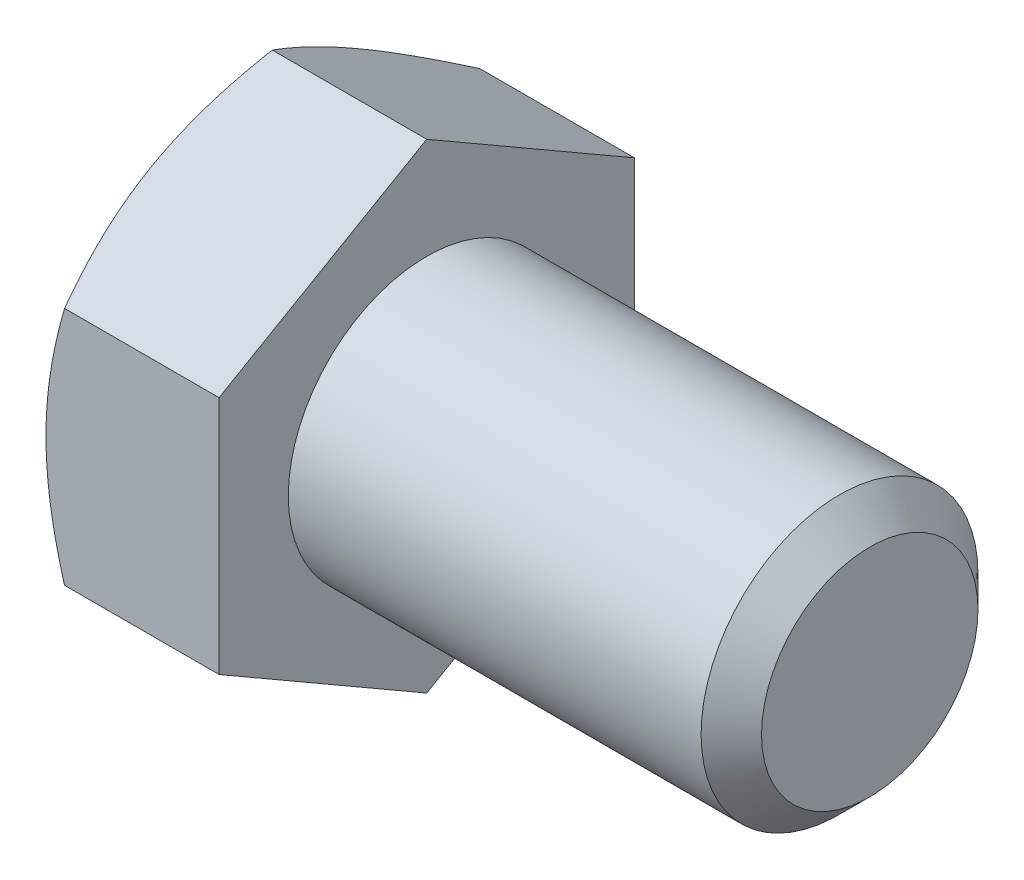
SolidWorks part; units mm, degrees
ref_plane "Front Plane" through (0, 0, 0) normal (0, 0, 1) x (1, 0, 0)
ref_plane "Top Plane" through (0, 0, 0) normal (0, 1, 0) x (1, 0, 0)
ref_plane "Right Plane" through (0, 0, 0) normal (1, 0, 0) x (0, 0, -1)
sketch "Sketch1" plane through (0, 0, 0) normal (0, 0, 1) x (1, 0, 0)
  line L0 (-17.6609, 0) -> (17.6609, 0) construction
  line L1 (17.6609, 7.9375) -> (17.6609, -7.9375) construction
  line L2 (-7.7391, 11.9062) -> (-7.7391, -11.9062) construction
  line L3 (-17.6609, 11.9062) -> (-17.6609, -11.9062) construction
  point P9 (-7.7391, 0)
  point P10 (9.5791, -7.9375)
  dimension "Screw Dia" = 15.875
  dimension "Hex" = 23.8125
  dimension "Head Ht" = 9.9219
  dimension "Screw Lenght" = 25.4
  dimension "D1" = 8.0818
ref_plane "Plane2" through (17.6609, 0, 0) normal (1, 0, 0) x (0, 0, -1)
sketch "Sketch5" plane through (17.6609, 0, 0) normal (1, 0, 0) x (0, 0, -1)
  circle A0 centre (0, 0) radius 7.9375
extrude "Boss-Extrude3" add sketch "Sketch5" against normal up to vertex (25.4 mm away) up to point (-7.7391, 0, 0)
sketch "Sketch9" plane through (17.6609, 0, 0) normal (1, 0, 0) x (0, 0, -1)
  circle A1 centre (0, 0) radius 7.9375
  circle A2 centre (0, 0) radius 7.9375
  dimension "D1" = 0
curve "Helix/Spiral1" pitch 2.3091 height 27.7091 turns 12 parameters "Pitch"=2.3091
chamfer "Chamfer1" distance 1.7318 angle 45 1 edges at (17.6609, 0, -7.9375)
sketch "Sketch10" plane through (0, 0, 0) normal (0, 0, 1) x (1, 0, 0)
  line L0 (17.6609, 7.9375) -> (18.5268, 6.4377)
  line L1 (18.5268, 6.4377) -> (18.8155, 6.4377)
  line L2 (18.8155, 6.4377) -> (19.6814, 7.9375)
  line L3 (17.6609, 7.9375) -> (19.6814, 7.9375)
  line L4 (18.6712, 7.9375) -> (18.6712, 6.4377) construction
  line L5 (18.0939, 7.1876) -> (19.2484, 7.1876) construction
  dimension "D1" = 60
  dimension "D2" = 0.2886
  dimension "D3" = 1.1545
sweep "Cut-Sweep1" [suppressed] cut profiles "Sketch10" path "Helix/Spiral1"
sketch "Sketch6" plane through (-7.7391, 0, 0) normal (-1, 0, 0) x (0, 0, 1)
  line L0 (0, 11.9062) -> (0, -11.9062) construction
  line L1 (11.9062, 6.8741) -> (0, 13.7482)
  line L2 (0, 13.7482) -> (-11.9063, 6.8741)
  line L3 (-11.9063, 6.8741) -> (-11.9063, -6.8741)
  line L4 (-11.9063, -6.8741) -> (0, -13.7482)
  line L5 (0, -13.7482) -> (11.9062, -6.8741)
  line L6 (11.9062, -6.8741) -> (11.9062, 6.8741)
  circle A0 centre (0, 0) radius 11.9062 construction
extrude "Boss-Extrude4" add sketch "Sketch6" along normal up to vertex (9.9219 mm away) up to point (-17.6609, -11.9062, 0)
sketch "Sketch7" plane through (-17.6609, 0, 0) normal (-1, 0, 0) x (0, 0, 1)
  circle A0 centre (0, 0) radius 11.9062 construction
  circle A1 centre (0, 0) radius 11.9062
sketch "Sketch8" plane through (-17.6609, 0, 0) normal (-1, 0, 0) x (0, 0, 1)
  circle A0 centre (0, 0) radius 11.9062 construction
  circle A1 centre (0, 0) radius 11.9062
extrude "Cut-Extrude3" cut sketch "Sketch8" against normal through all draft 60 flip side to cut
equation "\"D2@Sketch10\" = \"Pitch@Helix/Spiral1\"*.125"
equation "\"D3@Sketch10\" = \"Pitch@Helix/Spiral1\"*.5"
equation "\"D3@Helix/Spiral1\" = \"Screw Lenght@Sketch1\"+\"Pitch@Helix/Spiral1\""
equation "\"D1@Chamfer1\" = \"Pitch@Helix/Spiral1\"*.75"
equation "\"D1@Sketch1\" = \"Pitch@Helix/Spiral1\"*3.5"
